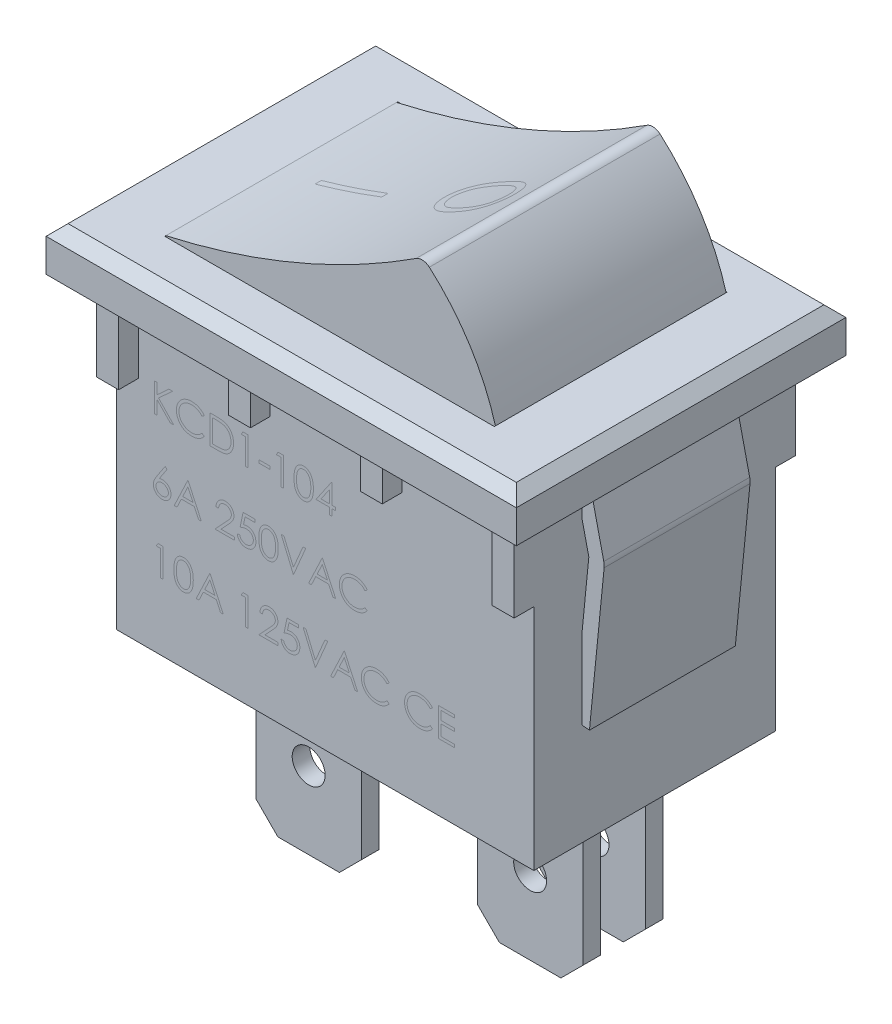
SolidWorks part; units mm, degrees
ref_plane "Front Plane" through (0, 0, 0) normal (0, 0, 1) x (1, 0, 0)
ref_plane "Top Plane" through (0, 0, 0) normal (0, 1, 0) x (1, 0, 0)
ref_plane "Right Plane" through (0, 0, 0) normal (1, 0, 0) x (0, 0, -1)
sketch "Sketch1" plane through (0, 0, 0) normal (0, 0, 1) x (1, 0, 0)
  line L1 (9.5, 7.2) -> (-9.5, 7.2)
  line L2 (9.5, 7.2) -> (9.5, -7.2)
  line L3 (9.5, -7.2) -> (-9.5, -7.2)
  line L4 (-9.5, 7.2) -> (-9.5, -7.2)
  line L5 (9.5, 7.2) -> (-9.5, -7.2) construction
  line L6 (9.5, -7.2) -> (-9.5, 7.2) construction
  point P0 (0, 0)
  dimension "D1" = 14.4
  dimension "D2" = 19
extrude "Boss-Extrude1" add sketch "Sketch1" along normal mid plane 11
sketch "Sketch2" plane through (0, 7.2, 0) normal (0, 1, 0) x (1, 0, 0)
  line L1 (10.7, 7.5) -> (-10.7, 7.5)
  line L2 (10.7, 7.5) -> (10.7, -7.5)
  line L3 (10.7, -7.5) -> (-10.7, -7.5)
  line L4 (-10.7, 7.5) -> (-10.7, -7.5)
  line L5 (10.7, 7.5) -> (-10.7, -7.5) construction
  line L6 (10.7, -7.5) -> (-10.7, 7.5) construction
  point P0 (0, 0)
  dimension "D1" = 15
  dimension "D2" = 21.4
extrude "Boss-Extrude2" add sketch "Sketch2" along normal blind 2
chamfer "Chamfer1" distance 0.5 angle 45 4 edges at (0, 9.2, -7.5) (10.7, 9.2, 0) (0, 9.2, 7.5) (-10.7, 9.2, 0)
sketch "Sketch11" plane through (0, 9.2, 0) normal (0, 1, 0) x (1, 0, 0)
  line L0 (-10.7, -7.5) -> (-10.7, 7.5) construction
  line L1 (-7.5, -5.3) -> (7.5, -5.3)
  line L2 (-7.5, -5.3) -> (-7.5, 5.3)
  line L3 (-7.5, 5.3) -> (7.5, 5.3)
  line L4 (7.5, -5.3) -> (7.5, 5.3)
  line L5 (-7.5, -5.3) -> (7.5, 5.3) construction
  line L6 (-7.5, 5.3) -> (7.5, -5.3) construction
  point P0 (0, 0)
  dimension "D1" = 3.2
  dimension "D2" = 10.6
extrude "Cut-Extrude6" cut sketch "Sketch11" against normal blind 0.25
sketch "Sketch3" plane through (0, 0, 0) normal (0, 0, 1) x (1, 0, 0)
  line L0 (7.5, 9.2) -> (4.2, 14.2) construction
  line L1 (-10.2, 9.2) -> (10.2, 9.2) construction
  line L2 (10.7, 8.7) -> (10.7, 7.2) construction
  line L4 (-10.7, 8.7) -> (-10.7, 7.2) construction
  line L5 (-7.5, 9.2) -> (7.5, 9.2) construction
  line L6 (-7.5, 9.2) -> (7.5, 9.2) construction
  line L7 (-7.5, 9.2) -> (-7.5, 8.9)
  line L8 (-7.5, 8.9) -> (7.5, 8.9)
  line L9 (7.5, 9.2) -> (7.5, 8.9)
  arc A0 (-7.5, 9.2) -> (3.89, 13.9963) centre (-15.1749, 43.3482) ccw
  arc A1 (4.4926, 13.9524) -> (7.5, 9.2) centre (-2.1129, 6.4445) cw
  arc A2 (3.89, 13.9963) -> (4.4926, 13.9524) centre (4.1623, 13.577) cw
  point P6 (-7.5, 9.2)
  dimension "D4" = 35
  dimension "D5" = 6.5
  dimension "D6" = 10
  dimension "D7" = 0.5
  dimension "D1" = 3.2
  dimension "D2" = 5
  dimension "D3" = 3.2
  dimension "D8" = 0.3
extrude "Boss-Extrude3" add sketch "Sketch3" along normal mid plane 10.5
sketch "Sketch5" plane through (0, -7.2, 0) normal (0, -1, 0) x (1, 0, 0)
  line L0 (-9.5, 5.5) -> (9.5, 5.5) construction
  line L1 (3.25, 1.82) -> (8.05, 1.82)
  line L2 (3.25, 1.82) -> (3.25, 1.02)
  line L3 (3.25, 1.02) -> (8.05, 1.02)
  line L4 (8.05, 1.82) -> (8.05, 1.02)
  line L5 (3.25, 1.82) -> (8.05, 1.02) construction
  line L6 (3.25, 1.02) -> (8.05, 1.82) construction
  line L7 (-5.95, -1.9) -> (-1.15, -1.9)
  line L8 (-5.95, -1.9) -> (-5.95, -2.7)
  line L9 (-5.95, -2.7) -> (-1.15, -2.7)
  line L10 (-1.15, -1.9) -> (-1.15, -2.7)
  line L11 (-5.95, -1.9) -> (-1.15, -2.7) construction
  line L12 (-5.95, -2.7) -> (-1.15, -1.9) construction
  line L13 (-9.5, -5.5) -> (9.5, -5.5) construction
  line L14 (9.5, 5.5) -> (9.5, -5.5) construction
  line L15 (0, 0) -> (-13.591, 0) construction
  line L16 (0, 0) -> (0, 9.8331) construction
  line L17 (3.25, -1.02) -> (8.05, -1.82) construction
  line L18 (3.25, -1.82) -> (8.05, -1.02) construction
  line L19 (8.05, -1.82) -> (8.05, -1.02)
  line L20 (3.25, -1.02) -> (8.05, -1.02)
  line L21 (3.25, -1.82) -> (3.25, -1.02)
  line L22 (3.25, -1.82) -> (8.05, -1.82)
  line L23 (-5.95, 2.7) -> (-1.15, 1.9) construction
  line L24 (-5.95, 1.9) -> (-1.15, 2.7) construction
  line L25 (-1.15, 1.9) -> (-1.15, 2.7)
  line L26 (-5.95, 2.7) -> (-1.15, 2.7)
  line L27 (-5.95, 1.9) -> (-5.95, 2.7)
  line L28 (-5.95, 1.9) -> (-1.15, 1.9)
  point P0 (5.65, 1.42)
  point P5 (-3.55, -2.3)
  point P24 (5.65, -1.42)
  point P29 (-3.55, 2.3)
  dimension "D1" = 4.8
  dimension "D2" = 0.8
  dimension "D3" = 14
  dimension "D4" = 3.68
  dimension "D5" = 2.8
  dimension "D6" = 1.45
extrude "Boss-Extrude5" add sketch "Sketch5" along normal blind 7.3
chamfer "Chamfer2" distance 1 angle 45 8 edges at (8.05, -14.5, 1.42) (3.25, -14.5, 1.42) (-1.15, -14.5, -2.3) (-5.95, -14.5, -2.3) (8.05, -14.5, -1.42) (3.25, -14.5, -1.42) (-1.15, -14.5, 2.3) (-5.95, -14.5, 2.3)
ref_plane "Plane2" through (-4.4202, 10.4969, 0) normal (0.3881, -0.9216, 0) x (-0.9216, -0.3881, 0)
sketch "Sketch7" plane through (-4.4202, 10.4969, 0) normal (0.3881, -0.9216, 0) x (-0.9216, -0.3881, 0)
  text T0 "<r90>I</r>" font "Century Gothic" height 3.2
  text T1 "<r90>0</r>"
wrap "Wrap1" sketch "Sketch7" wrap type scribe source sketch "Sketch7" face at (-1.6983, 11.3448, 0)
sketch "Sketch8" plane through (0, 0, 5.5) normal (0, 0, 1) x (1, 0, 0)
  text T0 "KCD1-104\r\n6A 250VAC\r\n10A 125VAC CE" font "Century Gothic" height 1.3
wrap "Wrap2" sketch "Sketch8" wrap type scribe source sketch "Sketch8" face at (0, 0, 5.5)
sketch "Sketch9" plane through (0, 0, 0) normal (0, 0, 1) x (1, 0, 0)
  line L0 (-9.5, 7.2) -> (-10.175, 4.25)
  line L1 (-10.175, 4.25) -> (-9.5, -2.55)
  line L2 (-9.5, 7.2) -> (-9.5, -7.2) construction
  line L3 (9.5, 7.2) -> (10.175, 4.25)
  line L4 (10.175, 4.25) -> (9.5, -2.55)
  line L5 (9.5, -7.2) -> (9.5, 7.2) construction
  line L6 (-10.7, 7.2) -> (10.7, 7.2) construction
  dimension "D1" = 2.95
  dimension "D2" = 6.8
  dimension "D3" = 20.35
extrude "Extrude-Thin14" add sketch "Sketch9" against normal mid plane 6.64 separate body thin thin type mid plane wall 0.7
sketch "Sketch10" plane through (0, 0, 3.32) normal (0, 0, 1) x (1, 0, 0)
  line L2 (-9.5, -7.2) -> (9.5, -7.2)
  line L3 (-9.5, -7.2) -> (-9.5, 7.2)
  line L4 (-9.5, 7.2) -> (9.5, 7.2)
  line L5 (9.5, -7.2) -> (9.5, 7.2)
extrude "Cut-Extrude5" cut sketch "Sketch10" against normal through all
sketch "Sketch12" plane through (0, 0, 2.7) normal (0, 0, 1) x (1, 0, 0)
  line L0 (-3.55, -7.2) -> (-3.55, -14.5) construction
  line L1 (-1.15, -7.2) -> (-5.95, -7.2) construction
  line L2 (-2.15, -14.5) -> (-4.95, -14.5) construction
  line L3 (5.65, -7.2) -> (5.65, -14.5) construction
  line L4 (8.05, -7.2) -> (3.25, -7.2) construction
  line L5 (7.05, -14.5) -> (4.25, -14.5) construction
  line L6 (-5.95, -11) -> (8.05, -11) construction
  line L7 (-5.95, -13.5) -> (-5.95, -7.2) construction
  line L8 (8.05, -13.5) -> (8.05, -7.2) construction
  circle A0 centre (-3.55, -11) radius 0.75
  circle A1 centre (5.65, -11) radius 0.75
  dimension "D2" = 1.5
  dimension "D3" = 1.5
  dimension "D1" = 3.5
extrude "Cut-Extrude7" cut sketch "Sketch12" against normal blind 10
sketch "Sketch13" plane through (0, 7.2, 0) normal (0, -1, 0) x (1, 0, 0)
  line L0 (0, 0) -> (0, 8.8925) construction
  line L1 (-9.5, 5.5) -> (-8.5, 5.5)
  line L2 (-9.5, 5.5) -> (-9.5, 6.4)
  line L3 (-9.5, 6.4) -> (-8.5, 6.4)
  line L4 (-8.5, 5.5) -> (-8.5, 6.4)
  line L5 (9.5, 5.5) -> (8.5, 5.5)
  line L6 (9.5, 5.5) -> (9.5, 6.4)
  line L7 (9.5, 6.4) -> (8.5, 6.4)
  line L8 (8.5, 5.5) -> (8.5, 6.4)
  line L9 (0, 0) -> (13.0895, 0) construction
  line L10 (9.5, -5.5) -> (9.5, -6.4)
  line L11 (9.5, -5.5) -> (8.5, -5.5)
  line L12 (8.5, -5.5) -> (8.5, -6.4)
  line L13 (9.5, -6.4) -> (8.5, -6.4)
  line L14 (-9.5, -5.5) -> (-8.5, -5.5)
  line L15 (-8.5, -5.5) -> (-8.5, -6.4)
  line L16 (-9.5, -6.4) -> (-8.5, -6.4)
  line L17 (-9.5, -5.5) -> (-9.5, -6.4)
  dimension "D1" = 6.4
  dimension "D2" = 1
extrude "Boss-Extrude6" add sketch "Sketch13" along normal blind 4
sketch "Sketch14" plane through (0, 7.2, 0) normal (0, -1, 0) x (1, 0, 0)
  line L0 (0, 0) -> (0, 8.0006) construction
  line L1 (0, 0) -> (13.8502, 0) construction
  line L2 (-9.5, 5.5) -> (9.5, 5.5) construction
  line L3 (-2.5, 5.5) -> (-3.5, 5.5)
  line L4 (-2.5, 5.5) -> (-2.5, 6.4)
  line L5 (-2.5, 6.4) -> (-3.5, 6.4)
  line L6 (-3.5, 5.5) -> (-3.5, 6.4)
  line L7 (2.5, 5.5) -> (2.5, 6.4)
  line L8 (2.5, 5.5) -> (3.5, 5.5)
  line L9 (3.5, 5.5) -> (3.5, 6.4)
  line L10 (2.5, 6.4) -> (3.5, 6.4)
  line L11 (3.5, -5.5) -> (3.5, -6.4)
  line L12 (2.5, -5.5) -> (3.5, -5.5)
  line L13 (2.5, -6.4) -> (3.5, -6.4)
  line L14 (2.5, -5.5) -> (2.5, -6.4)
  line L15 (-2.5, -5.5) -> (-2.5, -6.4)
  line L16 (-3.5, -5.5) -> (-3.5, -6.4)
  line L17 (-2.5, -5.5) -> (-3.5, -5.5)
  line L18 (-2.5, -6.4) -> (-3.5, -6.4)
  dimension "D1" = 6.4
  dimension "D2" = 1
  dimension "D3" = 2.5
extrude "Boss-Extrude7" add sketch "Sketch14" along normal blind 2.5
sketch "Sketch15" plane through (0, 0, 5.5) normal (0, 0, 1) x (1, 0, 0)
  line L0 (8.5, 7.2) -> (3.5, 7.2) construction
  line L1 (10.7, 8.7) -> (-10.7, 8.7) construction
  circle A0 centre (0, 6.2) radius 0.5
  point P7 (0, 8.7)
  dimension "D1" = 1
  dimension "D2" = 1
extrude "Cut-Extrude9" cut sketch "Sketch15" against normal blind 1.5
sketch "Sketch17" plane through (0, 0, 5.5) normal (0, 0, 1) x (1, 0, 0)
  circle A0 centre (0, 6.2) radius 0.75
  dimension "D1" = 1.5
extrude "Cut-Extrude10" cut sketch "Sketch17" against normal blind 0.5
sketch "Sketch18" plane through (0, 0, 0) normal (1, 0, 0) x (0, 0, -1)
  line L0 (-4, 6.2) -> (-6.4, 6.2) construction
  line L1 (-4, 6.7) -> (-4, 5.7) construction
  line L2 (-6.4, 4.7) -> (-6.4, 7.2) construction
  line L4 (-5, 6.95) -> (-5, 5.45) construction
  line L5 (-5.5, 6.95) -> (-5.5, 5.45) construction
  line L6 (-5.5, 6.2) -> (-5, 6.2)
  line L7 (-5, 6.95) -> (-5, 5.45)
  line L8 (-5, 6.95) -> (-5, 6.2)
  arc A0 (-5, 6.95) -> (-5.5, 6.2) centre (-4.6298, 6.1615) ccw
  dimension "D1" = 0
revolve "Revolve1" add sketch "Sketch18" angle 360 about L0
sketch "Sketch19" plane through (0, 0, 5.5) normal (0, 0, 1) x (1, 0, 0)
  line L0 (-0.05, 6.9483) -> (-0.05, 5.4517)
  line L1 (0, 6.95) -> (0, 5.45) construction
  line L2 (0.05, 6.9483) -> (0.05, 5.4517)
  line L3 (0, 6.2) -> (0.7319, 6.2) construction
  circle A2 centre (0, 6.2) radius 0.75 construction
  circle A3 centre (0, 6.2) radius 0.75 construction
  arc A4 (-0.05, 6.9483) -> (0.05, 6.9483) centre (0, 6.2) cw
  arc A5 (-0.05, 5.4517) -> (0.05, 5.4517) centre (0, 6.2) ccw
  dimension "D1" = 0.1
extrude "Cut-Extrude11" cut sketch "Sketch19" against normal blind 0.4
sketch "Sketch20" plane through (0, 0, 5.5) normal (0, 0, 1) x (1, 0, 0)
  line L0 (0.75, 6.2) -> (-0.75, 6.2) construction
  line L1 (-0.7483, 6.25) -> (0.7483, 6.25)
  line L2 (-0.7483, 6.15) -> (0.7483, 6.15)
  circle A0 centre (0, 6.2) radius 0.75 construction
  circle A1 centre (0, 6.2) radius 0.75 construction
  arc A4 (0.7483, 6.15) -> (0.7483, 6.25) centre (0, 6.2) ccw
  circle A5 centre (0, 6.2) radius 0.75
  arc A6 (-0.7483, 6.25) -> (-0.7483, 6.15) centre (0, 6.2) ccw
  dimension "D1" = 0.05
  dimension "D2" = 0
extrude "Cut-Extrude12" cut sketch "Sketch20" against normal blind 0.4
